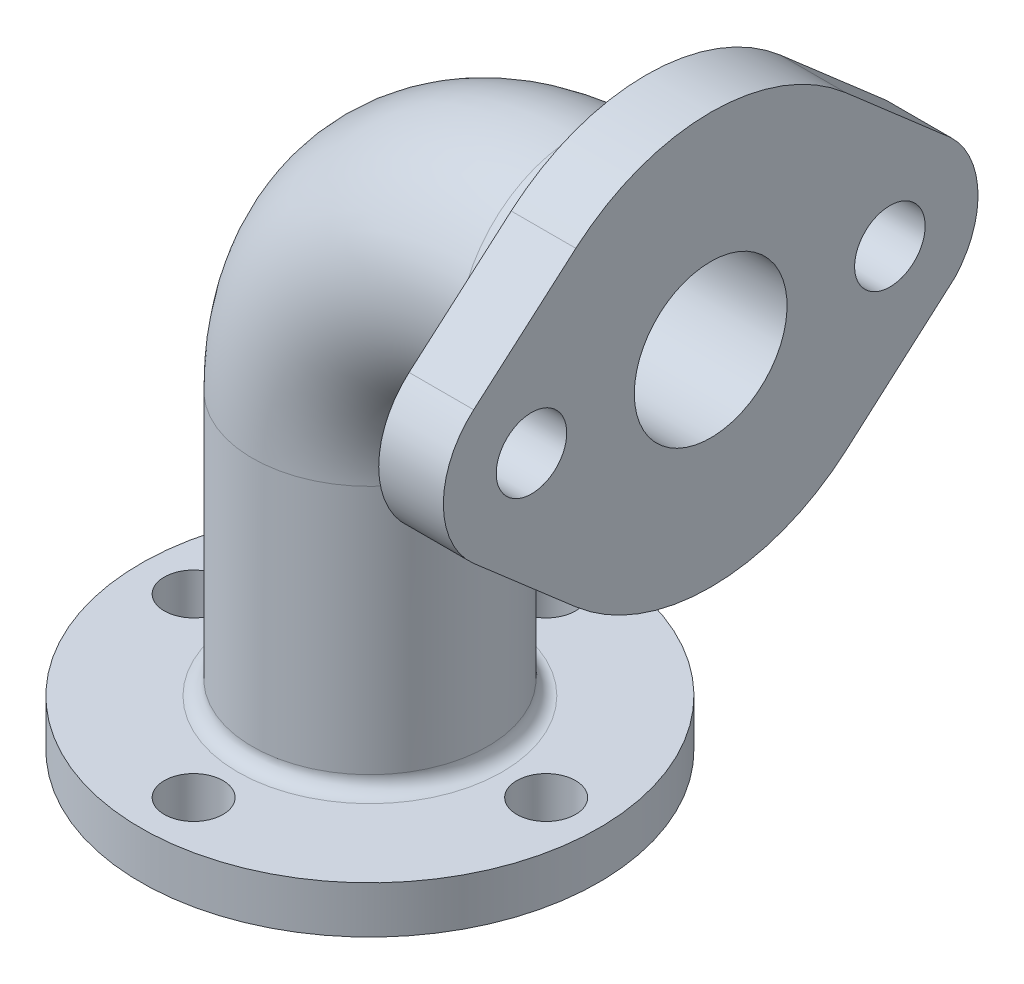
SolidWorks part; units mm, degrees
ref_plane "Alzado" through (0, 0, 0) normal (0, 0, 1) x (1, 0, 0)
ref_plane "Planta" through (0, 0, 0) normal (0, 1, 0) x (1, 0, 0)
ref_plane "Vista lateral" through (0, 0, 0) normal (1, 0, 0) x (0, 0, -1)
sketch "Croquis8" plane through (0, 0, 0) normal (0, 0, 1) x (1, 0, 0)
  line L0 (0, 0) -> (0, 53)
  line L1 (35, 88) -> (58, 88)
  arc A0 (35, 88) -> (0, 53) centre (35, 53) ccw
  point P7 (0, 88)
  dimension "D3" = 35
  dimension "D1" = 88
  dimension "D2" = 58
sketch "Croquis9" plane through (0, 0, 0) normal (0, 1, 0) x (1, 0, 0)
  circle A0 centre (0, 0) radius 39
  circle A1 centre (0, 0) radius 20
  dimension "D1" = 78
  dimension "D2" = 40
sweep "Barrer-Lámina1" add path "Croquis8" circular profile diameter 40 parameters "D1"=7, "D3"=40
sketch "Croquis166" plane through (58, 0, 0) normal (1, 0, 0) x (0, 0, -1)
  line L0 (-40.3361, 99.3248) -> (-22.9508, 114.4246)
  line L1 (40.8552, 98.8522) -> (22.9691, 114.4087)
  line L2 (41.5496, 77.8557) -> (23.0531, 61.6646)
  line L3 (-40.3361, 76.6752) -> (-22.9508, 61.5754)
  arc A0 (22.9691, 114.4087) -> (-22.9508, 114.4246) centre (0, 88) ccw
  circle A2 centre (-30.5, 88) radius 6
  circle A3 centre (30.5, 88) radius 6
  arc A4 (-40.3361, 99.3248) -> (-40.3361, 76.6752) centre (-30.5, 88) ccw
  arc A6 (41.5496, 77.8557) -> (40.8552, 98.8522) centre (30.5, 88) ccw
  arc A7 (-22.9508, 61.5754) -> (23.0531, 61.6646) centre (0, 88) ccw
  circle A9 centre (0, 88) radius 20
  dimension "D1" = 70
  dimension "D2" = 40
  dimension "D3" = 12
  dimension "D4" = 15
  dimension "D5" = 30
  dimension "D6" = 12
  dimension "D8" = 30.5
  dimension "D7" = 30.5
  dimension "D9" = 14.9109
extrude "Saliente-Extruir2" add sketch "Croquis166" against normal blind 11
sketch "Croquis167" plane through (0, 0, 0) normal (0, -1, 0) x (1, 0, 0)
  circle A0 centre (0, 0) radius 39
  circle A1 centre (0, 0) radius 13
extrude "Saliente-Extruir3" add sketch "Croquis167" against normal blind 8
sketch "Croquis168" plane through (0, 0, 0) normal (0, -1, 0) x (1, 0, 0)
  circle A0 centre (0, 30) radius 5
  circle A1 centre (0, -30) radius 5
  circle A2 centre (30, 0) radius 5
  circle A3 centre (-30, 0) radius 5
  circle A5 centre (0, 0) radius 39 construction
  dimension "D1" = 10
  dimension "D2" = 10
  dimension "D3" = 10
  dimension "D4" = 10
  dimension "D7" = 30
  dimension "D5" = 0
  dimension "D6" = 0
  dimension "D8" = 30
  dimension "D9" = 30
  dimension "D10" = 30
  dimension "D11" = 0
  dimension "D12" = 0
extrude "Cortar-Extruir2" cut sketch "Croquis168" against normal blind 15
fillet "Redondeo1" radius 2.5 1 edges at (47, 88, -20)
fillet "Redondeo2" radius 2.5 1 edges at (0, 8, -20)
